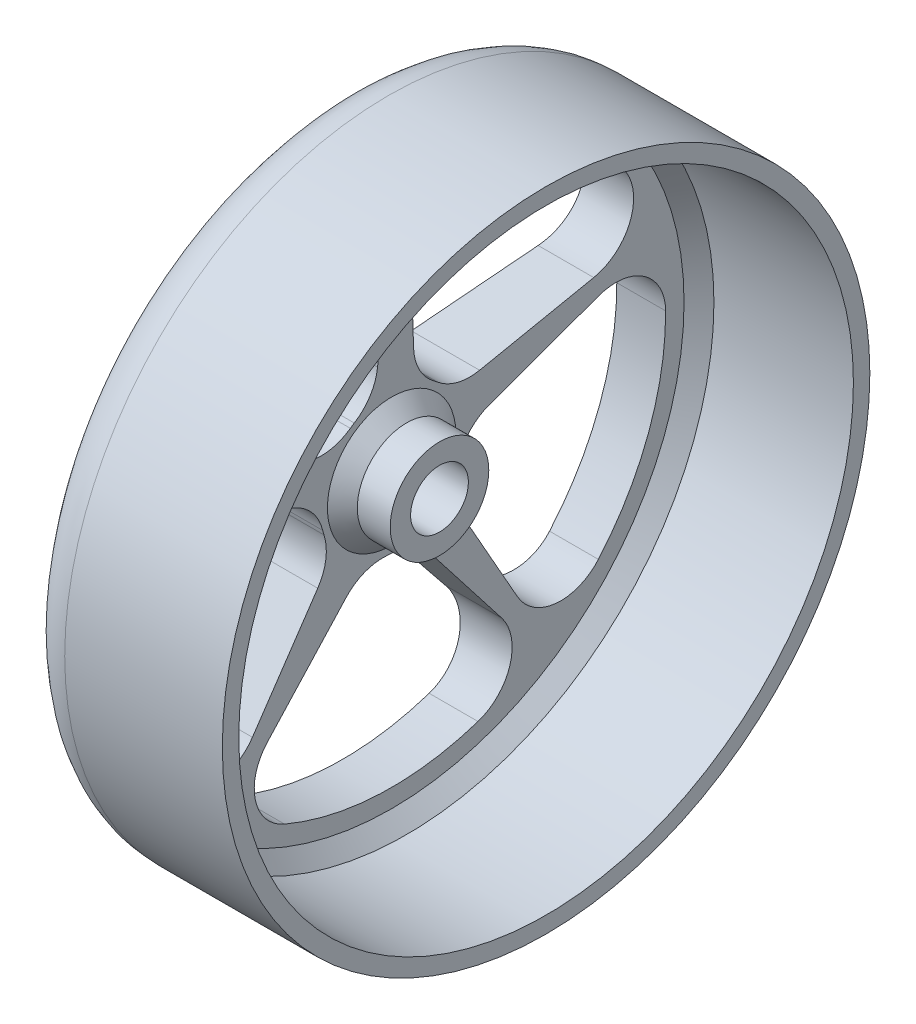
SolidWorks part; units mm, degrees
ref_plane "Front Plane" through (0, 0, 0) normal (0, 0, 1) x (1, 0, 0)
ref_plane "Top Plane" through (0, 0, 0) normal (0, 1, 0) x (1, 0, 0)
ref_plane "Right Plane" through (0, 0, 0) normal (1, 0, 0) x (0, 0, -1)
sketch "Sketch1" plane through (0, 0, 0) normal (0, 0, 1) x (1, 0, 0)
  line L0 (0, 0) -> (0, 3.5052)
  line L1 (0, 3.5052) -> (5.588, 3.5052)
  line L2 (5.588, 3.5052) -> (7.0249, 16.51)
  line L3 (7.0249, 16.51) -> (17.1087, 16.51)
  line L4 (17.1087, 16.51) -> (17.1087, 0)
  line L5 (17.1087, 0) -> (0, 0)
  dimension "D1" = 16.51
  dimension "D2" = 3.5052
  dimension "D3" = 5.588
  dimension "D4" = 10.0838
revolve "Revolve1" add sketch "Sketch1" angle 360 about L5
sketch "Sketch2" plane through (17.1087, 0, 0) normal (1, 0, 0) x (0, 0, -1)
  circle A0 centre (0, 0) radius 15.6718
extrude "Cut-Extrude1" cut sketch "Sketch2" against normal blind 7.874
sketch "Sketch3" plane through (9.2347, 0, 0) normal (1, 0, 0) x (0, 0, -1)
  circle A0 centre (0, 0) radius 2.5146
extrude "Extrude1" add sketch "Sketch3" along normal blind 2.4384
sketch "Sketch4" plane through (0, 0, 0) normal (-1, 0, 0) x (0, 0, 1)
  circle A0 centre (0, 0) radius 1.4732
  dimension "D1" = 2.9464
extrude "Cut-Extrude2" cut sketch "Sketch4" against normal through all
sketch "Sketch5" plane through (9.2347, 0, 0) normal (1, 0, 0) x (0, 0, -1)
  line L0 (-0.7192, 4.9485) -> (-0.045, 10.8493)
  line L2 (1.1172, 4.8741) -> (0.9228, 10.8101)
  line L3 (4.484, 2.2132) -> (10.3044, 3.3955)
  line L4 (4.9807, 0.4436) -> (10.5662, 2.4629)
  line L5 (3.4905, -3.5807) -> (6.4135, -8.7508)
  line L6 (1.961, -4.5999) -> (5.6075, -9.288)
  line L7 (-2.3268, -4.4261) -> (-6.3406, -8.8038)
  line L8 (-3.7688, -3.2865) -> (-7.1006, -8.2032)
  line L9 (-4.9285, 0.8452) -> (-10.3322, 3.3098)
  line L10 (-4.2903, 2.5687) -> (-9.9959, 4.2181)
  arc A0 (10.3044, 3.3955) -> (11.9763, 7.1923) centre (9.7988, 5.8846) ccw
  arc A1 (2.3378, 2.7632) -> (4.484, 2.2132) centre (3.9784, 4.7023) ccw
  arc A2 (3.4343, -1.143) -> (4.9807, 0.4436) centre (5.8443, -1.9451) cw
  arc A3 (0.9228, 10.8101) -> (4.2306, 13.314) centre (3.4614, 10.8933) cw
  arc A4 (-0.045, 10.8493) -> (-3.1394, 13.6127) centre (-2.5686, 11.1376) ccw
  arc A5 (10.5662, 2.4629) -> (13.9697, 0.0907) centre (11.4298, 0.0742) cw
  arc A6 (-1.9055, 3.0773) -> (-0.7192, 4.9485) centre (-3.2428, 5.2368) ccw
  arc A7 (2.1483, 2.913) -> (1.1172, 4.8741) centre (3.6559, 4.9572) cw
  arc A8 (6.4135, -8.7508) -> (10.5412, -9.1676) centre (8.6246, -7.5007) ccw
  arc A9 (3.3504, -1.3695) -> (3.4905, -3.5807) centre (5.7016, -2.3306) ccw
  arc A10 (-0.0258, -3.6194) -> (1.961, -4.5999) centre (-0.0439, -6.1593) cw
  arc A11 (5.6075, -9.288) -> (4.4032, -13.2579) centre (3.6026, -10.8474) cw
  arc A12 (-6.3406, -8.8038) -> (-5.4615, -12.8582) centre (-4.4685, -10.5203) ccw
  arc A13 (-0.2672, -3.6096) -> (-2.3268, -4.4261) centre (-0.4546, -6.1427) ccw
  arc A14 (-3.4502, -1.0939) -> (-3.7688, -3.2865) centre (-5.8714, -1.8616) cw
  arc A15 (-7.1006, -8.2032) -> (-11.2484, -8.2846) centre (-9.2032, -6.7783) cw
  arc A16 (-10.3322, 3.3098) -> (-13.9166, 1.2208) centre (-11.3863, 0.9988) ccw
  arc A17 (-3.5155, -0.8614) -> (-4.9285, 0.8452) centre (-5.9825, -1.4658) ccw
  arc A18 (-2.1066, 2.9433) -> (-4.2903, 2.5687) centre (-3.5849, 5.0088) cw
  arc A19 (-9.9959, 4.2181) -> (-11.3551, 8.1378) centre (-9.2905, 6.6582) cw
  arc A20 (-13.9166, 1.2208) -> (-11.2484, -8.2846) centre (0, 0) ccw
  arc A21 (-5.4615, -12.8582) -> (4.4032, -13.2579) centre (0, 0) ccw
  arc A22 (10.5412, -9.1676) -> (13.9697, 0.0907) centre (0, 0) ccw
  arc A23 (11.9763, 7.1923) -> (4.2306, 13.314) centre (0, 0) ccw
  arc A24 (-3.1394, 13.6127) -> (-11.3551, 8.1378) centre (0, 0) ccw
  arc A25 (-3.5155, -0.8614) -> (-3.4502, -1.0939) centre (0, 0) ccw
  arc A26 (-0.2672, -3.6096) -> (-0.0258, -3.6194) centre (0, 0) ccw
  arc A27 (3.3504, -1.3695) -> (3.4343, -1.143) centre (0, 0) ccw
  arc A28 (2.3378, 2.7632) -> (2.1483, 2.913) centre (0, 0) ccw
  arc A29 (-1.9055, 3.0773) -> (-2.1066, 2.9433) centre (0, 0) ccw
extrude "Cut-Extrude3" cut sketch "Sketch5" against normal through all
sketch "Sketch6" plane through (0, 0, 0) normal (0, 1, 0) x (1, 0, 0)
  circle A0 centre (3.81, 0) radius 0.5745
  point P0 (3.81, 0)
extrude "Cut-Extrude4" cut sketch "Sketch6" against normal through all and the other way through all
chamfer "Chamfer1" distance 0.762 angle 45 2 edges at (9.2347, 0, -2.5146) (9.2347, 0, -15.6718)
fillet "Fillet1" radius 1.016 2 edges at (5.588, 0, -3.5052) (0, 0, -3.5052)
fillet "Fillet2" radius 2.286 1 edges at (7.0249, 0, -16.51)
